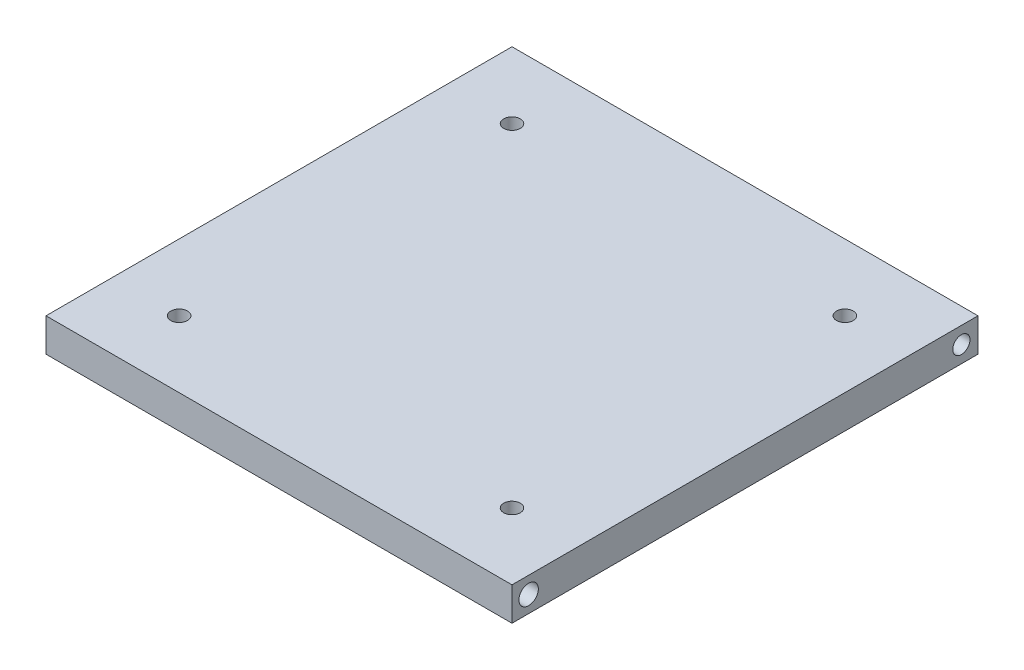
SolidWorks part; units mm, degrees
ref_plane "Front Plane" through (0, 0, 0) normal (0, 0, 1) x (1, 0, 0)
ref_plane "Top Plane" through (0, 0, 0) normal (0, 1, 0) x (1, 0, 0)
ref_plane "Right Plane" through (0, 0, 0) normal (1, 0, 0) x (0, 0, -1)
sketch "Sketch1" plane through (0, 0, 0) normal (0, 1, 0) x (1, 0, 0)
  line L1 (0, 0) -> (84, 0)
  line L2 (0, 0) -> (0, 84)
  line L3 (0, 84) -> (84, 84)
  line L4 (84, 0) -> (84, 84)
  dimension "D1" = 84
  dimension "D2" = 84
extrude "Boss-Extrude1" add sketch "Sketch1" along normal blind 6
sketch "Sketch2" plane through (0, 6, 0) normal (0, 1, 0) x (1, 0, 0)
  line L0 (84, 84) -> (0, 84) construction
  line L1 (0, 84) -> (0, 0) construction
  circle A0 centre (12, 72) radius 1.5
  dimension "D1" = 3
  dimension "D3" = 12
  dimension "D2" = 12
extrude "Cut-Extrude1" cut sketch "Sketch2" against normal blind 6
pattern_linear "LPattern1" count 2 spacing 60 along (1, 0, 0) count 2 spacing 60 along (0, 0, 1) of "Cut-Extrude1"
sketch "Sketch3" plane through (0, 0, 0) normal (-1, 0, 0) x (0, 0, 1)
  line L0 (-84, 3) -> (-3, 3) construction
  line L1 (-84, 6) -> (-84, 0) construction
  line L2 (0, 6) -> (0, 0) construction
  circle A0 centre (-81, 3) radius 1.5499
  circle A1 centre (-3, 3) radius 1.7482
  dimension "D1" = 3
  dimension "D2" = 3
extrude "Cut-Extrude2" cut sketch "Sketch3" against normal blind 10
ref_plane "Plane1" through (42, 0, 0) normal (-1, 0, 0) x (0, 0, 1)
mirror "Mirror1" about plane through (42, 0, 0) normal (-1, 0, 0) of "Cut-Extrude2"
